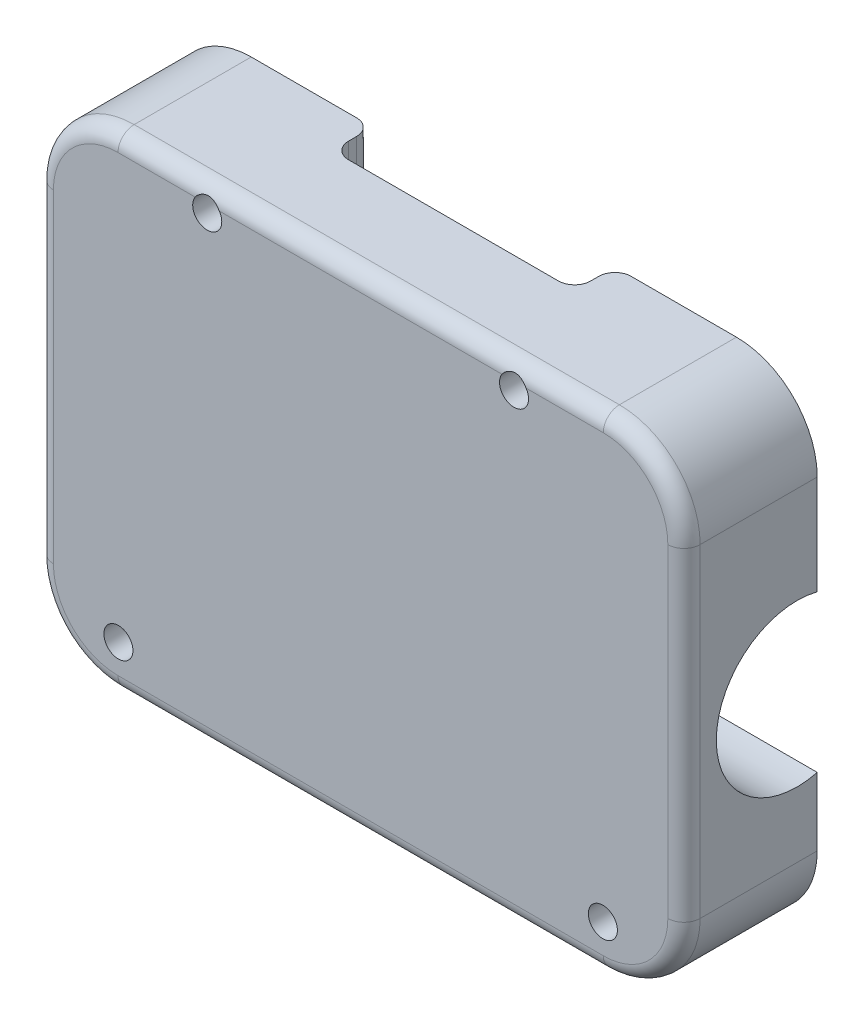
SolidWorks part; units mm, degrees
ref_plane "前视基准面" through (0, 0, 0) normal (0, 0, 1) x (1, 0, 0)
ref_plane "上视基准面" through (0, 0, 0) normal (0, 1, 0) x (1, 0, 0)
ref_plane "右视基准面" through (0, 0, 0) normal (1, 0, 0) x (0, 0, -1)
other "Configuration Table"
sketch "草图2" plane through (0, 0, 0) normal (0, 0, 1) x (1, 0, 0)
  line L0 (0, -60.1) -> (80.1, -60.1)
  line L1 (0, 0) -> (80.1, 0)
  line L2 (0, 0) -> (0, -60.1)
  line L3 (0, -60.1) -> (80.1, -60.1)
  line L4 (80.1, 0) -> (80.1, -60.1)
  line L5 (0, -62.1) -> (80.1, -62.1)
  dimension "D1" = 60.1
  dimension "D2" = 80.1
  dimension "D3" = 60.1
  dimension "D4" = 2
extrude "凸台-拉伸1" add sketch "草图2" along normal blind 28 contours L4 L1 L2 L0 region at (40.05, -30.05, 0)
sketch "草图3" plane through (0, 0, 0) normal (-1, 0, 0) x (0, 0, 1)
  line L0 (0, -32) -> (28, -32)
  line L1 (0, 0) -> (0, -60.1) construction
  line L2 (28, 0) -> (28, -60.1) construction
  line L3 (14, 0) -> (14, -60.1) construction
  line L4 (28, 0) -> (0, 0) construction
  line L5 (28, -60.1) -> (0, -60.1) construction
  circle A0 centre (14, -32) radius 10
  dimension "D2" = 20
  dimension "D1" = 32
extrude "切除-拉伸1" cut sketch "草图3" against normal blind 106 contours A0 L3 L0 | L0 L3 A0 | L3 L0 A0 | L3 A0 L0 region at (0, -27.7559, 9.7559) region at (0, -36.2441, 9.7559) region at (0, -27.7559, 18.2441) region at (0, -36.2441, 18.2441)
sketch "草图6" plane through (0, 0, 28) normal (0, 0, 1) x (1, 0, 0)
  line L0 (0, -30.05) -> (80.1, -30.05) construction
  line L1 (0, 0) -> (0, -60.1) construction
  line L2 (80.1, 0) -> (80.1, -60.1) construction
  line L3 (21.05, -3) -> (59.05, -3) construction
  line L4 (10.05, -54.5) -> (70.05, -54.5) construction
  line L5 (40.05, 0) -> (40.05, -60.1) construction
  line L6 (0, 0) -> (80.1, 0) construction
  line L7 (0, -60.1) -> (80.1, -60.1) construction
  circle A0 centre (21.05, -3) radius 1.8
  circle A1 centre (59.05, -3) radius 1.8
  circle A2 centre (10.05, -54.5) radius 1.8
  circle A3 centre (70.05, -54.5) radius 1.8
  dimension "D1" = 3.6
  dimension "D2" = 38
  dimension "D5" = 3
  dimension "D3" = 60
  dimension "D4" = 51.5
extrude "切除-拉伸2" cut sketch "草图6" against normal blind 106
sketch "草图7" plane through (0, 0, 28) normal (0, 0, 1) x (1, 0, 0)
  line L0 (0, -60.1) -> (0, -65.1)
  line L1 (0, -65.1) -> (80.1, -65.1)
  line L2 (80.1, -65.1) -> (80.1, -60.1)
  line L3 (0, -62.1) -> (80.1, -62.1)
  line L4 (80.1, -60.1) -> (80.1, 0)
  line L5 (80.1, 0) -> (0, 0)
  line L6 (0, 0) -> (0, -60.1)
  line L7 (0, -60.1) -> (80.1, -60.1)
  line L8 (80.1, -60.1) -> (80.1, 0)
  line L9 (80.1, 0) -> (0, 0)
  line L10 (0, 0) -> (0, -60.1)
  line L11 (0, -60.1) -> (80.1, -60.1)
  line L12 (40.05, 0) -> (40.05, -65.1) construction
  line L13 (27.55, -60.1) -> (27.55, -62.1)
  line L14 (52.55, -60.1) -> (52.55, -62.1)
  dimension "D2" = 5
  dimension "D3" = 2
  dimension "D4" = 25
  dimension "D1" = 0
sketch "草图9" plane through (0, 0, 0) normal (0, 1, 0) x (1, 0, 0)
  line L0 (0, -14) -> (80.1, -14) construction
  line L1 (0, -28) -> (0, 0) construction
  line L2 (80.1, -28) -> (80.1, 0) construction
  line L3 (40.05, 0) -> (40.05, -28) construction
  line L4 (0, -11.5) -> (25.05, -11.5)
  line L5 (0, -4) -> (0, -24) construction
  line L6 (25.05, -11.5) -> (25.05, -16.5)
  line L7 (80.1, 0) -> (0, 0)
  line L8 (0, 0) -> (0, -28)
  line L9 (0, -28) -> (80.1, -28)
  line L10 (80.1, -28) -> (80.1, 0)
  line L11 (80.1, 0) -> (0, 0)
  line L12 (0, 0) -> (0, -28)
  line L13 (0, -28) -> (80.1, -28)
  line L14 (80.1, -28) -> (80.1, 0)
  line L15 (25.05, -16.5) -> (55.05, -16.5)
  line L16 (55.05, -16.5) -> (55.05, -11.5)
  line L17 (55.05, -11.5) -> (80.1, -11.5)
  line M12 (80.1, 0) -> (0, 0)
  line M13 (0, 0) -> (0, -28)
  dimension "D1" = 0
  dimension "D2" = 5
  dimension "D3" = 30
extrude "切除-拉伸3" cut sketch "草图9" against normal blind 92 contours L16 L17 L14 L4 L6 L15 M12 M13 region at (40.05, 0, 6.9053)
fillet "圆角2" radius 2 8 edges at (55.05, -50.8912, 11.5) (55.05, -50.8912, 16.5) (55.05, -11.1588, 16.5) (55.05, -11.1588, 11.5) (25.05, -50.8912, 16.5) (25.05, -50.8912, 11.5) (25.05, -11.1588, 16.5) (25.05, -11.1588, 11.5)
fillet "圆角3" radius 10 4 edges at (0, 0, 19.75) (0, -60.1, 19.75) (80.1, -60.1, 19.75) (80.1, 0, 19.75)
fillet "圆角4" radius 2 8 edges at (2.9289, -57.1711, 28) (0, -30.05, 28) (2.9289, -2.9289, 28) (40.05, 0, 28) (77.1711, -2.9289, 28) (80.1, -30.05, 28) (77.1711, -57.1711, 28) (40.05, -60.1, 28)
